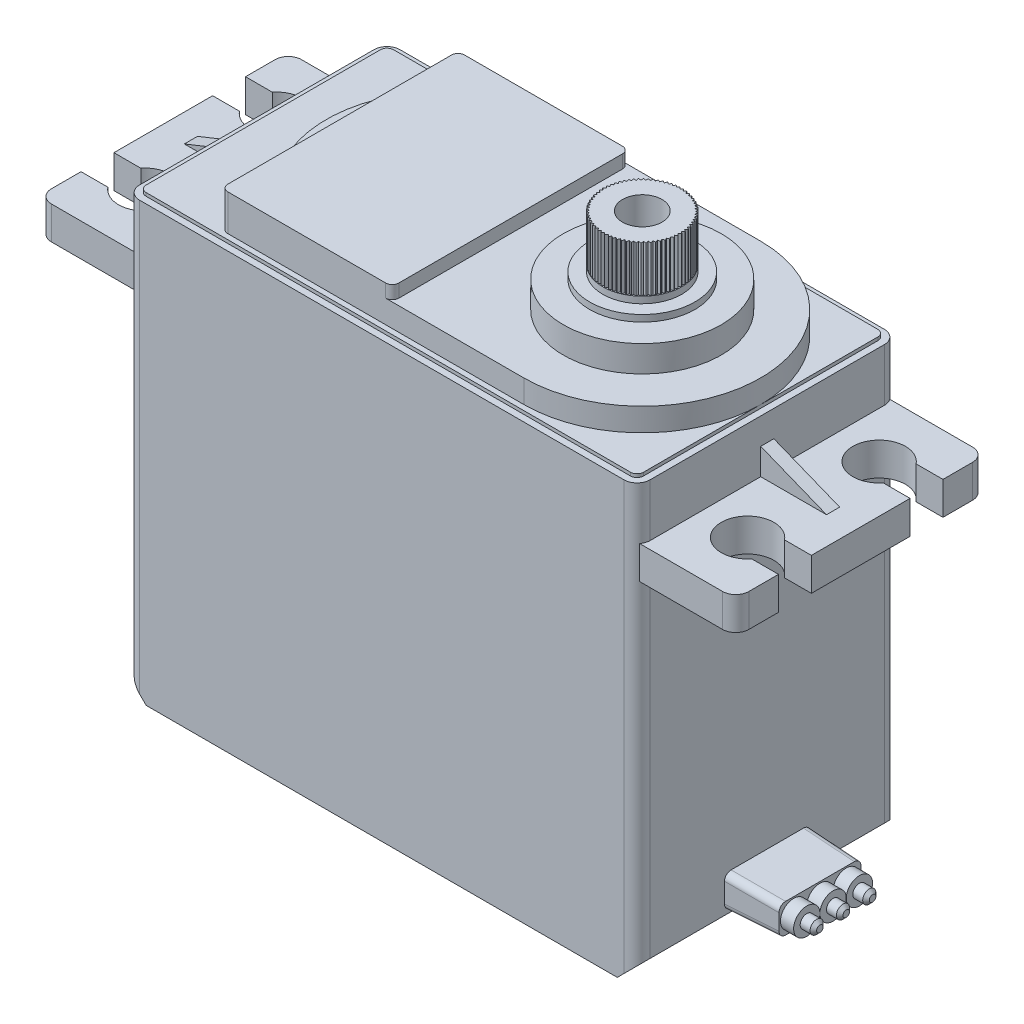
SolidWorks part; units mm, degrees
ref_plane "Front Plane" through (0, 0, 0) normal (0, 0, 1) x (1, 0, 0)
ref_plane "Top Plane" through (0, 0, 0) normal (0, 1, 0) x (1, 0, 0)
ref_plane "Right Plane" through (0, 0, 0) normal (1, 0, 0) x (0, 0, -1)
sketch "Sketch1" plane through (0, 0, 0) normal (0, 1, 0) x (1, 0, 0)
  line L2 (-19.4, 9.9) -> (-19.4, -9.9)
  line L3 (19.4, 9.9) -> (19.4, -9.9)
  line L4 (-19.4, -9.9) -> (19.4, -9.9)
  line L5 (-19.4, 9.9) -> (19.4, 9.9)
extrude "Extrude1" add sketch "Sketch1" along normal blind 26.5
sketch "Sketch2" plane through (0, 26.5, 0) normal (0, 1, 0) x (-1, 0, 0)
  line L0 (19.4, -9.9) -> (-19.4, -9.9)
  line L1 (-19.4, -9.9) -> (-19.4, -9.5)
  line L2 (24.4612, 6.25) -> (26.5, 6.25)
  line L3 (-26.5, -8.5) -> (-26.5, -6.25)
  line L4 (-19.4, 9.9) -> (19.4, 9.9)
  line L5 (24.4612, -3.75) -> (26.5, -3.75)
  line L6 (-19.4, 9.5) -> (-19.4, 9.9)
  line L7 (24.4612, 3.75) -> (26.5, 3.75)
  line L8 (0, 0) -> (0, 8.5) construction
  line L9 (26.5, 6.25) -> (26.5, 8.5)
  line L10 (24.4612, -6.25) -> (26.5, -6.25)
  line L11 (-19.4, 9.5) -> (-25.5, 9.5)
  line L12 (26.5, -3.75) -> (26.5, 3.75)
  line L13 (-19.4, -9.5) -> (-25.5, -9.5)
  line L14 (19.4, -9.5) -> (25.5, -9.5)
  line L15 (-26.5, -3.75) -> (-26.5, 3.75)
  line L16 (-24.4612, -6.25) -> (-26.5, -6.25)
  line L17 (19.4, 9.5) -> (25.5, 9.5)
  line L18 (-26.5, 6.25) -> (-26.5, 8.5)
  line L19 (-24.4612, 3.75) -> (-26.5, 3.75)
  line L20 (19.4, 9.5) -> (19.4, 9.9)
  line L21 (26.5, -8.5) -> (26.5, -6.25)
  line L22 (-24.4612, -3.75) -> (-26.5, -3.75)
  line L23 (19.4, -9.9) -> (19.4, -9.5)
  line L24 (0, 0) -> (-10.2456, 0) construction
  line L25 (-24.4612, 6.25) -> (-26.5, 6.25)
  line L26 (-22.9, 5) -> (-26.6668, 5) construction
  line L27 (-26.5, -3.75) -> (-26.5, -6.25) construction
  line L28 (-24.4612, 6.25) -> (-24.4612, 3.75) construction
  arc A0 (25.5, -9.5) -> (26.5, -8.5) centre (25.5, -8.5) ccw
  arc A1 (26.5, 8.5) -> (25.5, 9.5) centre (25.5, 8.5) ccw
  arc A2 (-24.4612, -6.25) -> (-24.4612, -3.75) centre (-22.9, -5) ccw
  arc A3 (-24.4612, 3.75) -> (-24.4612, 6.25) centre (-22.9, 5) ccw
  arc A4 (24.4612, 3.75) -> (24.4612, 6.25) centre (22.9, 5) cw
  arc A5 (24.4612, -6.25) -> (24.4612, -3.75) centre (22.9, -5) cw
  arc A6 (-26.5, 8.5) -> (-25.5, 9.5) centre (-25.5, 8.5) cw
  arc A7 (-25.5, -9.5) -> (-26.5, -8.5) centre (-25.5, -8.5) cw
  dimension "D5" = 2.5
  dimension "D1" = 53
  dimension "D3" = 10
  dimension "D4" = 2
  dimension "D7" = 1
  dimension "D2" = 3.6
  dimension "D6" = 19
chamfer "Chamfer1" distance 1.5 angle 45 2 edges at (-19.4, 0, 0) (19.4, 0, 0)
extrude "Extrude5" add sketch "Sketch2" along normal blind 2.5
sketch "Sketch3" plane through (0, 29, 0) normal (0, 1, 0) x (-1, 0, 0)
  line L0 (19.4, -9.9) -> (-19.4, -9.9)
  line L1 (-19.4, -9.9) -> (-19.4, 9.9)
  line L2 (-19.4, 9.9) -> (19.4, 9.9)
  line L3 (19.4, 9.9) -> (19.4, -9.9)
extrude "Extrude6" add sketch "Sketch3" along normal blind 4
fillet "Fillet1" radius 1 4 edges at (-19.4, 17.25, -9.9) (19.4, 17.25, -9.9) (-19.4, 17.25, 9.9) (19.4, 17.25, 9.9)
sketch "Sketch5" plane through (0, 33, 0) normal (0, 1, 0) x (-1, 0, 0)
  line L3 (13.1, -8.5) -> (13.1, 8.5)
  line L4 (12.6, 9) -> (-9.9, 9)
  line L5 (12.6, -9) -> (-9.9, -9)
  arc A3 (12.6, 9) -> (13.1, 8.5) centre (12.6, 8.5) cw
  arc A4 (-9.9, 9) -> (-9.9, -9) centre (-9.9, 0) ccw
  arc A5 (13.1, -8.5) -> (12.6, -9) centre (12.6, -8.5) cw
extrude "Extrude8" add sketch "Sketch5" along normal blind 2
sketch "Sketch6" plane through (0, 35, 0) normal (0, 1, 0) x (-1, 0, 0)
  line L6 (0.6, -9) -> (12.6, -9)
  line L7 (13.1, -8.5) -> (13.1, 8.5)
  line L8 (0.6, 9) -> (12.6, 9)
  line L9 (0.1, -8.5) -> (0.1, 8.5)
  arc A0 (13.1, -8.5) -> (12.6, -9) centre (12.6, -8.5) cw
  arc A1 (0.1, -8.5) -> (0.6, -9) centre (0.6, -8.5) ccw
  arc A2 (13.1, 8.5) -> (12.6, 9) centre (12.6, 8.5) ccw
  arc A3 (0.1, 8.5) -> (0.6, 9) centre (0.6, 8.5) cw
  dimension "D1" = 0.5
extrude "Extrude9" add sketch "Sketch6" along normal blind 1
sketch "Sketch7" plane through (0, 33, 0) normal (0, 1, 0) x (-1, 0, 0)
  line L0 (12.6, -5) -> (12.6, 5)
  arc A0 (12.6, -5) -> (12.6, 5) centre (5.1167, 0) ccw
extrude "Extrude10" add sketch "Sketch7" along normal blind 2.5
sketch "Sketch8" plane through (0, 33, 0) normal (0, 1, 0) x (-1, 0, 0)
  line L4 (18.9, -8.9) -> (18.9, 8.9)
  line L5 (18.4, 9.4) -> (-18.4, 9.4)
  line L6 (-18.9, -8.9) -> (-18.9, 8.9)
  line L7 (18.4, -9.4) -> (-18.4, -9.4)
  arc A4 (18.4, 9.4) -> (18.9, 8.9) centre (18.4, 8.9) cw
  arc A5 (-18.9, 8.9) -> (-18.4, 9.4) centre (-18.4, 8.9) cw
  arc A6 (-18.4, -9.4) -> (-18.9, -8.9) centre (-18.4, -8.9) cw
  arc A7 (18.9, -8.9) -> (18.4, -9.4) centre (18.4, -8.9) cw
extrude "Extrude11" add sketch "Sketch8" along normal blind 0.25
sketch "Sketch9" plane through (0, 35, 0) normal (0, 1, 0) x (-1, 0, 0)
  circle A0 centre (-9.9, 0) radius 6
extrude "Extrude12" add sketch "Sketch9" along normal blind 2
sketch "Sketch10" plane through (0, 37, 0) normal (0, 1, 0) x (-1, 0, 0)
  circle A0 centre (-9.9, 0) radius 4
extrude "Extrude13" add sketch "Sketch10" along normal blind 0.5
sketch "Sketch11" plane through (0, 37.5, 0) normal (0, 1, 0) x (-1, 0, 0)
  circle A0 centre (-9.9, 0) radius 3
extrude "Extrude14" add sketch "Sketch11" along normal blind 4 separate body
sketch "Sketch22" plane through (19.4, 0, 0) normal (1, 0, 0) x (0, 0, -1)
  line L0 (-2, 3) -> (2, 3) construction
  circle A0 centre (-2, 3) radius 1
  circle A1 centre (0, 3) radius 1
  circle A2 centre (2, 3) radius 1
  circle A4 centre (0, 3) radius 0.5
  circle A5 centre (2, 3) radius 0.5
  circle A6 centre (-2, 3) radius 0.5
  point P3 (2.8313, 3.8338)
  point P4 (0, 3.5414)
  point P6 (-0.9187, 3.8338)
  point P7 (2, 3.5414)
  point P15 (0.9563, 3.8338)
  dimension "D1" = 1
  dimension "D2" = 0.5
  dimension "D3" = 3
extrude "Extrude25" add sketch "Sketch22" along normal blind 5 separate body contours A6 | L0 A4 | A5 | L0 A4 region at (19.4, 3, 2.9717) region at (19.4, 3.9717, -2) region at (19.4, 3.9717, 0)
sketch "Sketch24" plane through (19.4, 0, 0) normal (1, 0, 0) x (0, 0, -1)
  circle A0 centre (-2, 3) radius 0.5 construction
  circle A1 centre (0, 3) radius 0.5 construction
  circle A2 centre (2, 3) radius 0.5 construction
  circle A3 centre (-2, 3) radius 0.5
  circle A4 centre (0, 3) radius 0.5
  circle A5 centre (2, 3) radius 0.5
extrude "Extrude26" add sketch "Sketch24" along normal blind 6
chamfer "Chamfer2" distance 0.25 angle 45 3 edges at (25.4, 3, 1.5) (25.4, 3, -0.5) (25.4, 3, -2.5)
sketch "Sketch25" plane through (19.4, 0, 0) normal (1, 0, 0) x (0, 0, -1)
  line L1 (-3.25, 1.75) -> (3.25, 1.75)
  line L2 (-3.25, 1.75) -> (-3.25, 4.25)
  line L3 (-3.25, 4.25) -> (3.25, 4.25)
  line L4 (3.25, 1.75) -> (3.25, 4.25)
  line L5 (-3.25, 1.75) -> (3.25, 4.25) construction
  line L6 (-3.25, 4.25) -> (3.25, 1.75) construction
  circle A0 centre (-2, 3) radius 0.5 construction
  point P0 (0, 3)
  dimension "D1" = 1.25
  dimension "D2" = 1.25
extrude "Extrude27" add sketch "Sketch25" along normal blind 4 draft 2 separate body
fillet "Fillet8" radius 0.5 4 edges at (21.4, 1.8198, 3.1802) (21.4, 1.8198, -3.1802) (21.4, 4.1802, -3.1802) (21.4, 4.1802, 3.1802)
hole_wizard "Ø3.0 (3) Diameter Hole1" positions "Sketch27" profile "Sketch26" hole size "Ø3.0" standard "Ansi Metric"
sketch "Sketch27" plane through (0, 41.5, 0) normal (0, 1, 0) x (-1, 0, 0)
  circle A0 centre (-9.9, 0) radius 3 construction
  point P0 (-9.9, 0)
sketch "Sketch26" plane through (9.9, 41.5, 0) normal (1, 0, 0) x (0, 0, 1)
  line L0 (0, 0) -> (0, 5.9013)
  line L1 (0, 5.9013) -> (1.5, 5)
  line L2 (1.5, 5) -> (1.5, 0)
  line L5 (1.5, 0) -> (0, 0)
  line L10 (0, 5.9013) -> (-1.5, 5) construction
  line L11 (0, -6.35) -> (0, 107.95) construction
  dimension "Hole Dia." = 3
  dimension "Hole Depth" = 5
  dimension "Drill Angle" = 118
sketch "Sketch28" plane through (0, 0, 0) normal (0, 0, 1) x (1, 0, 0)
  line L0 (-24.4, 29) -> (-19.4, 31)
  line L1 (-25.5, 29) -> (-19.2, 29) construction
  line L2 (-19.4, 29) -> (-19.4, 33) construction
  dimension "D1" = 5
  dimension "D2" = 2
rib "Rib2" sketch "Sketch28" sketch "Sketch28" thickness 1 extrusion direction parallel to sketch draft on no parameters "D1"=1
mirror "Mirror1" about plane through (0, 0, 0) normal (1, 0, 0) of "Rib2"
sketch "Sketch30" plane through (0, 41.5, 0) normal (0, 1, 0) x (1, 0, 0)
  line L0 (9.775, 2.9974) -> (9.9, 2.85)
  line L1 (9.9, 2.85) -> (10.025, 2.9974)
  line L2 (9.9, 2.85) -> (9.9, 3) construction
  line L3 (10.1555, 2.8385) -> (10.2932, 2.9741)
  line L4 (10.0442, 2.9965) -> (10.1555, 2.8385)
  line L5 (10.4089, 2.8042) -> (10.5582, 2.9269)
  line L6 (10.3122, 2.9715) -> (10.4089, 2.8042)
  line L7 (10.6582, 2.7473) -> (10.8179, 2.8561)
  line L8 (10.5769, 2.9226) -> (10.6582, 2.7473)
  line L9 (10.9014, 2.6683) -> (11.0702, 2.7623)
  line L10 (10.8362, 2.8502) -> (10.9014, 2.6683)
  line L11 (11.1366, 2.5678) -> (11.3131, 2.6463)
  line L12 (11.0879, 2.7548) -> (11.1366, 2.5678)
  line L13 (11.3618, 2.4466) -> (11.5447, 2.509)
  line L14 (11.3301, 2.6372) -> (11.3618, 2.4466)
  line L15 (11.5752, 2.3057) -> (11.763, 2.3515)
  line L16 (11.5607, 2.4984) -> (11.5752, 2.3057)
  line L17 (11.7751, 2.1463) -> (11.9662, 2.175)
  line L18 (11.778, 2.3395) -> (11.7751, 2.1463)
  line L19 (11.96, 1.9695) -> (12.1529, 1.981)
  line L20 (11.9801, 2.1617) -> (11.96, 1.9695)
  line L21 (12.1282, 1.7769) -> (12.3214, 1.7711)
  line L22 (12.1655, 1.9666) -> (12.1282, 1.7769)
  line L23 (12.2785, 1.5701) -> (12.4704, 1.5469)
  line L24 (12.3327, 1.7556) -> (12.2785, 1.5701)
  line L25 (12.4097, 1.3505) -> (12.5987, 1.3103)
  line L26 (12.4803, 1.5304) -> (12.4097, 1.3505)
  line L27 (12.5207, 1.1201) -> (12.7053, 1.0631)
  line L28 (12.6071, 1.293) -> (12.5207, 1.1201)
  line L29 (12.6105, 0.8807) -> (12.7893, 0.8074)
  line L30 (12.7121, 1.0451) -> (12.6105, 0.8807)
  line L31 (12.6785, 0.6342) -> (12.8501, 0.5451)
  line L32 (12.7944, 0.7888) -> (12.6785, 0.6342)
  line L33 (12.7242, 0.3826) -> (12.887, 0.2785)
  line L34 (12.8535, 0.5262) -> (12.7242, 0.3826)
  line L35 (12.7471, 0.1279) -> (12.9, 0.0096)
  line L36 (12.8888, 0.2594) -> (12.7471, 0.1279)
  line L37 (12.7471, -0.1279) -> (12.8888, -0.2594)
  line L38 (12.9, -0.0096) -> (12.7471, -0.1279)
  line L39 (12.7242, -0.3826) -> (12.8535, -0.5262)
  line L40 (12.887, -0.2785) -> (12.7242, -0.3826)
  line L41 (12.6785, -0.6342) -> (12.7944, -0.7888)
  line L42 (12.8501, -0.5451) -> (12.6785, -0.6342)
  line L43 (12.6105, -0.8807) -> (12.7121, -1.0451)
  line L44 (12.7893, -0.8074) -> (12.6105, -0.8807)
  line L45 (12.5207, -1.1201) -> (12.6071, -1.293)
  line L46 (12.7053, -1.0631) -> (12.5207, -1.1201)
  line L47 (12.4097, -1.3505) -> (12.4803, -1.5304)
  line L48 (12.5987, -1.3103) -> (12.4097, -1.3505)
  line L49 (12.2785, -1.5701) -> (12.3327, -1.7556)
  line L50 (12.4704, -1.5469) -> (12.2785, -1.5701)
  line L51 (12.1282, -1.7769) -> (12.1655, -1.9666)
  line L52 (12.3214, -1.7711) -> (12.1282, -1.7769)
  line L53 (11.96, -1.9695) -> (11.9801, -2.1617)
  line L54 (12.1529, -1.981) -> (11.96, -1.9695)
  line L55 (11.7751, -2.1463) -> (11.778, -2.3395)
  line L56 (11.9662, -2.175) -> (11.7751, -2.1463)
  line L57 (11.5752, -2.3057) -> (11.5607, -2.4984)
  line L58 (11.763, -2.3515) -> (11.5752, -2.3057)
  line L59 (11.3618, -2.4466) -> (11.3301, -2.6372)
  line L60 (11.5447, -2.509) -> (11.3618, -2.4466)
  line L61 (11.1366, -2.5678) -> (11.0879, -2.7548)
  line L62 (11.3131, -2.6463) -> (11.1366, -2.5678)
  line L63 (10.9014, -2.6683) -> (10.8362, -2.8502)
  line L64 (11.0702, -2.7623) -> (10.9014, -2.6683)
  line L65 (10.6582, -2.7473) -> (10.5769, -2.9226)
  line L66 (10.8179, -2.8561) -> (10.6582, -2.7473)
  line L67 (10.4089, -2.8042) -> (10.3122, -2.9715)
  line L68 (10.5582, -2.9269) -> (10.4089, -2.8042)
  line L69 (10.1555, -2.8385) -> (10.0442, -2.9965)
  line L70 (10.2932, -2.9741) -> (10.1555, -2.8385)
  line L71 (9.9, -2.85) -> (9.775, -2.9974)
  line L72 (10.025, -2.9974) -> (9.9, -2.85)
  line L73 (9.6445, -2.8385) -> (9.5068, -2.9741)
  line L74 (9.7558, -2.9965) -> (9.6445, -2.8385)
  line L75 (9.3911, -2.8042) -> (9.2418, -2.9269)
  line L76 (9.4878, -2.9715) -> (9.3911, -2.8042)
  line L77 (9.1418, -2.7473) -> (8.9821, -2.8561)
  line L78 (9.2231, -2.9226) -> (9.1418, -2.7473)
  line L79 (8.8986, -2.6683) -> (8.7298, -2.7623)
  line L80 (8.9638, -2.8502) -> (8.8986, -2.6683)
  line L81 (8.6634, -2.5678) -> (8.4869, -2.6463)
  line L82 (8.7121, -2.7548) -> (8.6634, -2.5678)
  line L83 (8.4382, -2.4466) -> (8.2553, -2.509)
  line L84 (8.4699, -2.6372) -> (8.4382, -2.4466)
  line L85 (8.2248, -2.3057) -> (8.037, -2.3515)
  line L86 (8.2393, -2.4984) -> (8.2248, -2.3057)
  line L87 (8.0249, -2.1463) -> (7.8338, -2.175)
  line L88 (8.022, -2.3395) -> (8.0249, -2.1463)
  line L89 (7.84, -1.9695) -> (7.6471, -1.981)
  line L90 (7.8199, -2.1617) -> (7.84, -1.9695)
  line L91 (7.6718, -1.7769) -> (7.4786, -1.7711)
  line L92 (7.6345, -1.9666) -> (7.6718, -1.7769)
  line L93 (7.5215, -1.5701) -> (7.3296, -1.5469)
  line L94 (7.4673, -1.7556) -> (7.5215, -1.5701)
  line L95 (7.3903, -1.3505) -> (7.2013, -1.3103)
  line L96 (7.3197, -1.5304) -> (7.3903, -1.3505)
  line L97 (7.2793, -1.1201) -> (7.0947, -1.0631)
  line L98 (7.1929, -1.293) -> (7.2793, -1.1201)
  line L99 (7.1895, -0.8807) -> (7.0107, -0.8074)
  line L100 (7.0879, -1.0451) -> (7.1895, -0.8807)
  line L101 (7.1215, -0.6342) -> (6.9499, -0.5451)
  line L102 (7.0056, -0.7888) -> (7.1215, -0.6342)
  line L103 (7.0758, -0.3826) -> (6.913, -0.2785)
  line L104 (6.9465, -0.5262) -> (7.0758, -0.3826)
  line L105 (7.0529, -0.1279) -> (6.9, -0.0096)
  line L106 (6.9112, -0.2594) -> (7.0529, -0.1279)
  line L107 (7.0529, 0.1279) -> (6.9112, 0.2594)
  line L108 (6.9, 0.0096) -> (7.0529, 0.1279)
  line L109 (7.0758, 0.3826) -> (6.9465, 0.5262)
  line L110 (6.913, 0.2785) -> (7.0758, 0.3826)
  line L111 (7.1215, 0.6342) -> (7.0056, 0.7888)
  line L112 (6.9499, 0.5451) -> (7.1215, 0.6342)
  line L113 (7.1895, 0.8807) -> (7.0879, 1.0451)
  line L114 (7.0107, 0.8074) -> (7.1895, 0.8807)
  line L115 (7.2793, 1.1201) -> (7.1929, 1.293)
  line L116 (7.0947, 1.0631) -> (7.2793, 1.1201)
  line L117 (7.3903, 1.3505) -> (7.3197, 1.5304)
  line L118 (7.2013, 1.3103) -> (7.3903, 1.3505)
  line L119 (7.5215, 1.5701) -> (7.4673, 1.7556)
  line L120 (7.3296, 1.5469) -> (7.5215, 1.5701)
  line L121 (7.6718, 1.7769) -> (7.6345, 1.9666)
  line L122 (7.4786, 1.7711) -> (7.6718, 1.7769)
  line L123 (7.84, 1.9695) -> (7.8199, 2.1617)
  line L124 (7.6471, 1.981) -> (7.84, 1.9695)
  line L125 (8.0249, 2.1463) -> (8.022, 2.3395)
  line L126 (7.8338, 2.175) -> (8.0249, 2.1463)
  line L127 (8.2248, 2.3057) -> (8.2393, 2.4984)
  line L128 (8.037, 2.3515) -> (8.2248, 2.3057)
  line L129 (8.4382, 2.4466) -> (8.4699, 2.6372)
  line L130 (8.2553, 2.509) -> (8.4382, 2.4466)
  line L131 (8.6634, 2.5678) -> (8.7121, 2.7548)
  line L132 (8.4869, 2.6463) -> (8.6634, 2.5678)
  line L133 (8.8986, 2.6683) -> (8.9638, 2.8502)
  line L134 (8.7298, 2.7623) -> (8.8986, 2.6683)
  line L135 (9.1418, 2.7473) -> (9.2231, 2.9226)
  line L136 (8.9821, 2.8561) -> (9.1418, 2.7473)
  line L137 (9.3911, 2.8042) -> (9.4878, 2.9715)
  line L138 (9.2418, 2.9269) -> (9.3911, 2.8042)
  line L139 (9.6445, 2.8385) -> (9.7558, 2.9965)
  line L140 (9.5068, 2.9741) -> (9.6445, 2.8385)
  circle A0 centre (9.9, 0) radius 3 construction
  arc A1 (10.025, 2.9974) -> (9.775, 2.9974) centre (9.9, 0) ccw
  arc A2 (10.2932, 2.9741) -> (10.0442, 2.9965) centre (9.9, 0) ccw
  arc A3 (10.5582, 2.9269) -> (10.3122, 2.9715) centre (9.9, 0) ccw
  arc A4 (10.8179, 2.8561) -> (10.5769, 2.9226) centre (9.9, 0) ccw
  arc A5 (11.0702, 2.7623) -> (10.8362, 2.8502) centre (9.9, 0) ccw
  arc A6 (11.3131, 2.6463) -> (11.0879, 2.7548) centre (9.9, 0) ccw
  arc A7 (11.5447, 2.509) -> (11.3301, 2.6372) centre (9.9, 0) ccw
  arc A8 (11.763, 2.3515) -> (11.5607, 2.4984) centre (9.9, 0) ccw
  arc A9 (11.9662, 2.175) -> (11.778, 2.3395) centre (9.9, 0) ccw
  arc A10 (12.1529, 1.981) -> (11.9801, 2.1617) centre (9.9, 0) ccw
  arc A11 (12.3214, 1.7711) -> (12.1655, 1.9666) centre (9.9, 0) ccw
  arc A12 (12.4704, 1.5469) -> (12.3327, 1.7556) centre (9.9, 0) ccw
  arc A13 (12.5987, 1.3103) -> (12.4803, 1.5304) centre (9.9, 0) ccw
  arc A14 (12.7053, 1.0631) -> (12.6071, 1.293) centre (9.9, 0) ccw
  arc A15 (12.7893, 0.8074) -> (12.7121, 1.0451) centre (9.9, 0) ccw
  arc A16 (12.8501, 0.5451) -> (12.7944, 0.7888) centre (9.9, 0) ccw
  arc A17 (12.887, 0.2785) -> (12.8535, 0.5262) centre (9.9, 0) ccw
  arc A18 (12.9, 0.0096) -> (12.8888, 0.2594) centre (9.9, 0) ccw
  arc A19 (12.8888, -0.2594) -> (12.9, -0.0096) centre (9.9, 0) ccw
  arc A20 (12.8535, -0.5262) -> (12.887, -0.2785) centre (9.9, 0) ccw
  arc A21 (12.7944, -0.7888) -> (12.8501, -0.5451) centre (9.9, 0) ccw
  arc A22 (12.7121, -1.0451) -> (12.7893, -0.8074) centre (9.9, 0) ccw
  arc A23 (12.6071, -1.293) -> (12.7053, -1.0631) centre (9.9, 0) ccw
  arc A24 (12.4803, -1.5304) -> (12.5987, -1.3103) centre (9.9, 0) ccw
  arc A25 (12.3327, -1.7556) -> (12.4704, -1.5469) centre (9.9, 0) ccw
  arc A26 (12.1655, -1.9666) -> (12.3214, -1.7711) centre (9.9, 0) ccw
  arc A27 (11.9801, -2.1617) -> (12.1529, -1.981) centre (9.9, 0) ccw
  arc A28 (11.778, -2.3395) -> (11.9662, -2.175) centre (9.9, 0) ccw
  arc A29 (11.5607, -2.4984) -> (11.763, -2.3515) centre (9.9, 0) ccw
  arc A30 (11.3301, -2.6372) -> (11.5447, -2.509) centre (9.9, 0) ccw
  arc A31 (11.0879, -2.7548) -> (11.3131, -2.6463) centre (9.9, 0) ccw
  arc A32 (10.8362, -2.8502) -> (11.0702, -2.7623) centre (9.9, 0) ccw
  arc A33 (10.5769, -2.9226) -> (10.8179, -2.8561) centre (9.9, 0) ccw
  arc A34 (10.3122, -2.9715) -> (10.5582, -2.9269) centre (9.9, 0) ccw
  arc A35 (10.0442, -2.9965) -> (10.2932, -2.9741) centre (9.9, 0) ccw
  arc A36 (9.775, -2.9974) -> (10.025, -2.9974) centre (9.9, 0) ccw
  arc A37 (9.5068, -2.9741) -> (9.7558, -2.9965) centre (9.9, 0) ccw
  arc A38 (9.2418, -2.9269) -> (9.4878, -2.9715) centre (9.9, 0) ccw
  arc A39 (8.9821, -2.8561) -> (9.2231, -2.9226) centre (9.9, 0) ccw
  arc A40 (8.7298, -2.7623) -> (8.9638, -2.8502) centre (9.9, 0) ccw
  arc A41 (8.4869, -2.6463) -> (8.7121, -2.7548) centre (9.9, 0) ccw
  arc A42 (8.2553, -2.509) -> (8.4699, -2.6372) centre (9.9, 0) ccw
  arc A43 (8.037, -2.3515) -> (8.2393, -2.4984) centre (9.9, 0) ccw
  arc A44 (7.8338, -2.175) -> (8.022, -2.3395) centre (9.9, 0) ccw
  arc A45 (7.6471, -1.981) -> (7.8199, -2.1617) centre (9.9, 0) ccw
  arc A46 (7.4786, -1.7711) -> (7.6345, -1.9666) centre (9.9, 0) ccw
  arc A47 (7.3296, -1.5469) -> (7.4673, -1.7556) centre (9.9, 0) ccw
  arc A48 (7.2013, -1.3103) -> (7.3197, -1.5304) centre (9.9, 0) ccw
  arc A49 (7.0947, -1.0631) -> (7.1929, -1.293) centre (9.9, 0) ccw
  arc A50 (7.0107, -0.8074) -> (7.0879, -1.0451) centre (9.9, 0) ccw
  arc A51 (6.9499, -0.5451) -> (7.0056, -0.7888) centre (9.9, 0) ccw
  arc A52 (6.913, -0.2785) -> (6.9465, -0.5262) centre (9.9, 0) ccw
  arc A53 (6.9, -0.0096) -> (6.9112, -0.2594) centre (9.9, 0) ccw
  arc A54 (6.9112, 0.2594) -> (6.9, 0.0096) centre (9.9, 0) ccw
  arc A55 (6.9465, 0.5262) -> (6.913, 0.2785) centre (9.9, 0) ccw
  arc A56 (7.0056, 0.7888) -> (6.9499, 0.5451) centre (9.9, 0) ccw
  arc A57 (7.0879, 1.0451) -> (7.0107, 0.8074) centre (9.9, 0) ccw
  arc A58 (7.1929, 1.293) -> (7.0947, 1.0631) centre (9.9, 0) ccw
  arc A59 (7.3197, 1.5304) -> (7.2013, 1.3103) centre (9.9, 0) ccw
  arc A60 (7.4673, 1.7556) -> (7.3296, 1.5469) centre (9.9, 0) ccw
  arc A61 (7.6345, 1.9666) -> (7.4786, 1.7711) centre (9.9, 0) ccw
  arc A62 (7.8199, 2.1617) -> (7.6471, 1.981) centre (9.9, 0) ccw
  arc A63 (8.022, 2.3395) -> (7.8338, 2.175) centre (9.9, 0) ccw
  arc A64 (8.2393, 2.4984) -> (8.037, 2.3515) centre (9.9, 0) ccw
  arc A65 (8.4699, 2.6372) -> (8.2553, 2.509) centre (9.9, 0) ccw
  arc A66 (8.7121, 2.7548) -> (8.4869, 2.6463) centre (9.9, 0) ccw
  arc A67 (8.9638, 2.8502) -> (8.7298, 2.7623) centre (9.9, 0) ccw
  arc A68 (9.2231, 2.9226) -> (8.9821, 2.8561) centre (9.9, 0) ccw
  arc A69 (9.4878, 2.9715) -> (9.2418, 2.9269) centre (9.9, 0) ccw
  arc A70 (9.7558, 2.9965) -> (9.5068, 2.9741) centre (9.9, 0) ccw
  dimension "D1" = 0.25
  dimension "D2" = 0.15
  dimension "D3" = 70
extrude "Cut-Extrude1" cut sketch "Sketch30" against normal blind 3.5
